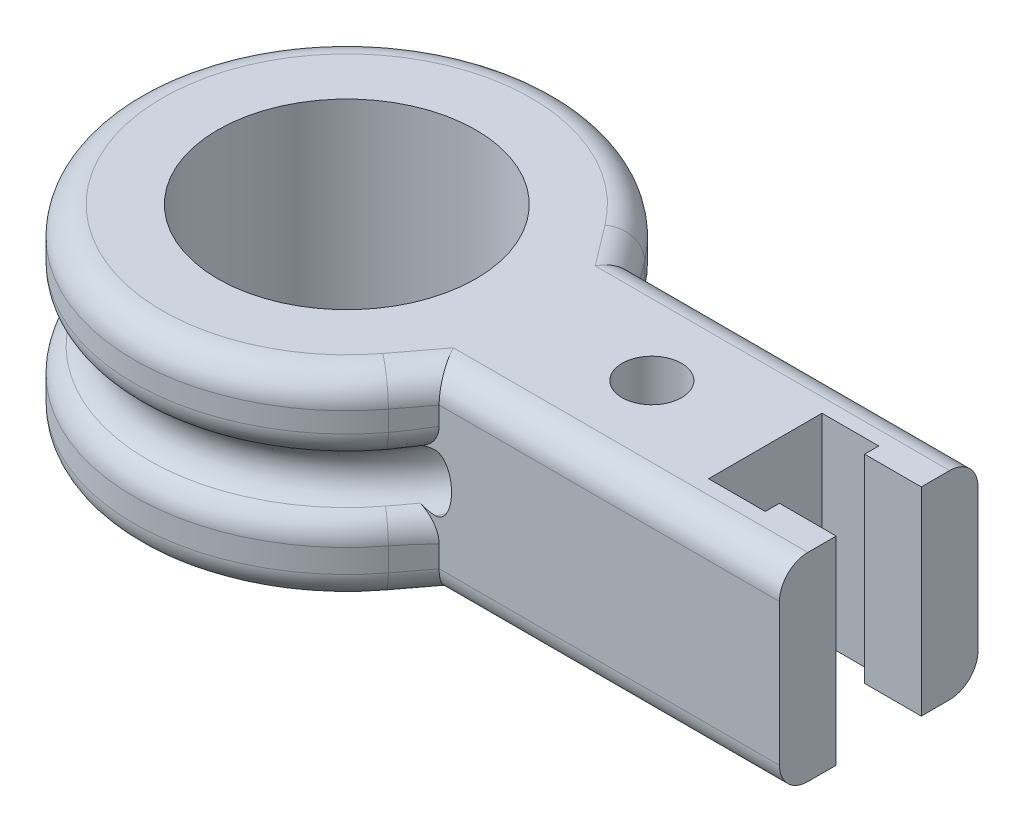
SolidWorks part; units mm, degrees
ref_plane "Front Plane" through (0, 0, 0) normal (0, 0, 1) x (1, 0, 0)
ref_plane "Top Plane" through (0, 0, 0) normal (0, 1, 0) x (1, 0, 0)
ref_plane "Right Plane" through (0, 0, 0) normal (1, 0, 0) x (0, 0, -1)
sketch "Sketch1" plane through (0, 0, 0) normal (0, 1, 0) x (1, 0, 0)
  line L0 (-10.3258, 0) -> (22.3498, 0) construction
  line L1 (6.7556, 3.5) -> (5.984, 4.5213)
  line L2 (6.7556, -3.5) -> (18.7556, -3.5)
  line L4 (6.7556, 3.5) -> (18.7556, 3.5)
  line L6 (6.7556, -3.5) -> (18.7556, 3.5) construction
  line L7 (6.7556, 3.5) -> (18.7556, -3.5) construction
  line L8 (6.7556, -3.5) -> (5.984, -4.5213)
  line L15 (18.7556, 3.5) -> (18.7556, -3.5)
  arc A0 (5.984, 4.5213) -> (5.984, -4.5213) centre (0, 0) ccw
  circle A1 centre (0, 0) radius 4.55
  point P5 (12.7556, 0)
  dimension "D1" = 15
  dimension "D2" = 9.1
  dimension "D3" = 12
extrude "Boss-Extrude2" add sketch "Sketch1" along normal blind 7 contours A1 | L2 L15 L4 L1 A0 L8 region at (0, 0, 0)
sketch "Sketch5" plane through (0, 7, 0) normal (0, 1, 0) x (1, 0, 0)
  line L0 (21.1623, 0) -> (11.2502, 0) construction
  line L1 (18.7556, 3.5) -> (18.7556, -3.5) construction
  line L2 (16.7556, -2) -> (14.7556, -2)
  line L3 (16.7556, -2) -> (16.7556, -1.5)
  line L4 (16.7556, 2) -> (14.7556, 2)
  line L5 (14.7556, -2) -> (14.7556, 2)
  line L6 (16.7556, -2) -> (14.7556, 2) construction
  line L7 (16.7556, 2) -> (14.7556, -2) construction
  line L8 (16.7556, -1.5) -> (18.7556, -1.5)
  line L10 (16.7556, 1.5) -> (18.7556, 1.5)
  line L11 (18.7556, -1.5) -> (18.7556, 1.5)
  line L12 (16.7556, -1.5) -> (18.7556, 1.5) construction
  line L13 (16.7556, 1.5) -> (18.7556, -1.5) construction
  line L14 (16.7556, 1.5) -> (16.7556, 2)
  point P3 (17.7556, 0)
  point P4 (15.7556, 0)
  dimension "D1" = 4
  dimension "D2" = 2
  dimension "D3" = 2
  dimension "D4" = 3
extrude "Cut-Extrude3" cut sketch "Sketch5" against normal through all
sketch "Sketch2" plane through (0, 0, 0) normal (1, 0, 0) x (0, -1, 0)
  line L0 (0, -0.6001) -> (0, 7.5244) construction
  line L3 (-7.3353, 0) -> (0.2116, 0) construction
  line L4 (-7.3353, 7.5) -> (0.2244, 7.5) construction
  ellipse E0 centre (-3.5555, 7.5) end of major axis (-2.5555, 7.5) minor radius 1 (-4.5555, 7.5) -> (-2.5555, 7.5) ccw
  ellipse E1 centre (-3.5555, 7.5) end of major axis (-2.5555, 7.5) minor radius 0.5 (-2.5555, 7.5) -> (-4.5555, 7.5) ccw
  point P5 (-4.0532, 7.5)
  point P6 (-2.3212, 6.5715)
  point P20 (0, 7.5)
  dimension "D1" = 1
  dimension "D3" = 0.5
revolve "Cut-Revolve1" cut sketch "Sketch2" angle 360 about L3
fillet "Fillet4" radius 1 6 edges at (6.3698, 0, -4.0107) (6.3698, 0, 4.0107) (6.3698, 7, -4.0107) (6.3698, 7, 4.0107) (-7.5, 0, 0) (-7.5, 7, 0)
sketch "Sketch4" plane through (0, 7, 0) normal (0, 1, 0) x (1, 0, 0)
  line L0 (-9.5617, 0) -> (25.0544, 0) construction
  line L2 (6.7556, 3.5) -> (6.7556, -3.5) construction
  circle A0 centre (10.7556, 0) radius 1.05
  point P6 (6.7556, 0)
  point P13 (0, 0)
  dimension "D1" = 2.1
  dimension "D2" = 4
extrude "Cut-Extrude2" cut sketch "Sketch4" against normal blind 10
fillet "Fillet7" radius 1 6 edges at (6.2854, 4.5549, 4.1224) (6.2854, 4.5549, -4.1224) (6.4478, 2.5586, -3.9074) (6.4478, 2.5586, 3.9074) (-7.5, 2.5555, 0) (-7.5, 4.5555, 0)
fillet "Fillet8" radius 1 4 edges at (12.129, 0, -3.5) (12.129, 0, 3.5) (12.129, 7, -3.5) (12.129, 7, 3.5)
